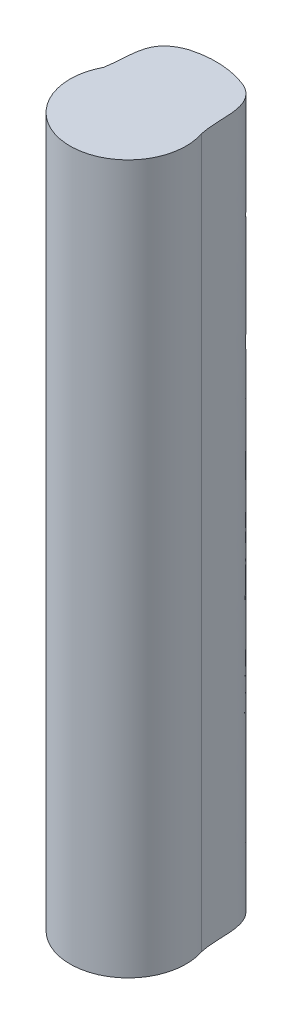
SolidWorks part; units mm, degrees
ref_plane "Front Plane" through (0, 0, 0) normal (0, 0, 1) x (1, 0, 0)
ref_plane "Top Plane" through (0, 0, 0) normal (0, 1, 0) x (1, 0, 0)
ref_plane "Right Plane" through (0, 0, 0) normal (1, 0, 0) x (0, 0, -1)
sketch "Sketch1" plane through (0, 0, 0) normal (0, 1, 0) x (1, 0, 0)
  circle A0 centre (0, 0) radius 25.273
  circle A1 centre (0, 0) radius 25.273
extrude "Boss-Extrude1" add sketch "Sketch1" along normal blind 203.2 contours A0
sketch "Sketch2" plane through (0, 203.2, 0) normal (0, 1, 0) x (1, 0, 0)
  circle A0 centre (0, 0) radius 16.6497
  circle A1 centre (0, 0) radius 25.273 construction
  spline S0 degree 3 poles (-16.1314, 4.1218) (-13.2336, 7.9922) (-17.8746, 25.2503) (1.5488, 26.2881) (6.0478, 24.5387) knots 0 0 0 0 0.459844 1 1 1 1
  spline S1 degree 3 poles (16.1314, 4.1218) (13.5509, 11.4427) (18.5011, 21.9118) (6.0478, 24.5387) knots 0 0 0 0 1 1 1 1
  point P9 (0, 0)
  point P12 (0, 0)
  point P16 (5.2355, 24.5387)
  circle M2 centre (0, 0) radius 25.273
extrude "Cut-Extrude1" cut sketch "Sketch2" against normal blind 203.2 contours S1 A0 S0 M2 region at (17.2224, 203.2, -2.1655)
